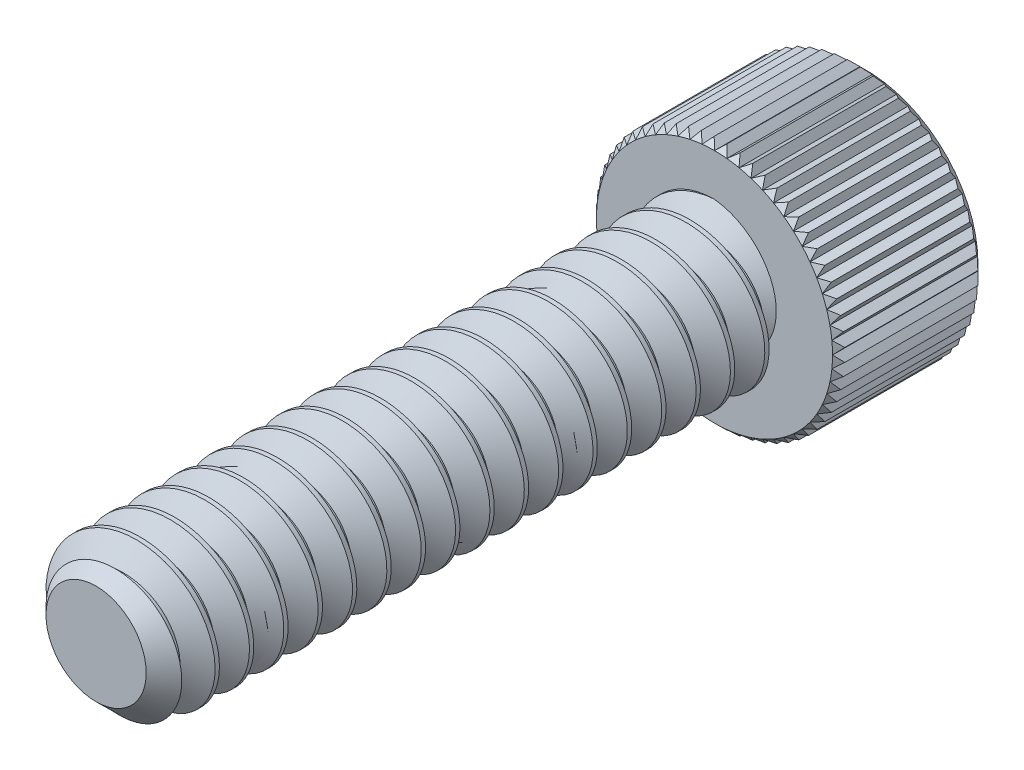
SolidWorks part; units mm, degrees
note: '?' marks a value the reader was unsure of.
ref_plane "Front Plane" through (0, 0, 0) normal (0, 0, 1) x (1, 0, 0)
ref_plane "Top Plane" through (0, 0, 0) normal (0, 1, 0) x (1, 0, 0)
ref_plane "Right Plane" through (0, 0, 0) normal (1, 0, 0) x (0, 0, -1)
sketch "Sketch0" plane through (0, 0, 0) normal (1, 0, 0) x (0, 0, -1)
  line L0 (0, 0) -> (14.2875, 0) construction
  point P2 (17.7927, 0)
  point P4 (0, 0)
  dimension "D1" = 14.2875
  dimension "D2" = 3.5052
  dimension "Min Thread" = 0
sketch "Sketch1" plane through (0, 0, 0) normal (0, 0, 1) x (1, 0, 0)
  circle A0 centre (0, 0) radius 1.7526
  dimension "OD" = 3.5052
extrude "Extrude1" add sketch "Sketch1" against normal blind 14.2875
sketch "Sketch2" plane through (0, 0, 0) normal (0, 0, 1) x (1, 0, 0)
  circle A0 centre (0, 0) radius 1.7526 construction
  circle A1 centre (0, 0) radius 1.7526
curve "Helix/Spiral1" pitch 0.7937 height 15.0812 turns 19 parameters "pitch"=0.7937
chamfer "Chamfer3" distance 0.5953 angle 45 1 edges at (1.7526, 0, 0)
sketch "Sketch3" plane through (0, 0, 0) normal (1, 0, 0) x (0, 0, -1)
  line L0 (-0.6945, 1.7526) -> (-0.3969, 1.237)
  line L1 (-0.3969, 1.237) -> (-0.2977, 1.237)
  line L2 (-0.2977, 1.237) -> (0, 1.7526)
  line L3 (-0.6945, 1.7526) -> (0, 1.7526)
  line L4 (-0.3473, 1.7526) -> (-0.3473, 1.237) construction
  line L5 (-0.5457, 1.4948) -> (-0.1488, 1.4948) construction
  line L6 (0, 1.7526) -> (0, -1.7526) construction
  dimension "D1" = 0.0992
  dimension "D2" = 0.3969
  dimension "D3" = 60
sweep "Cut-Sweep1" cut profiles "Sketch3" path "Helix/Spiral1"
sketch "Sketch5" plane through (0, 0, 0) normal (1, 0, 0) x (0, 0, -1)
  line L0 (14.2875, -1.2539) -> (14.2875, 1.2505) construction
  line L1 (14.2875, 1.7526) -> (0, 1.7526)
  line L2 (14.2875, 1.7526) -> (14.2875, 0)
  line L3 (14.2875, 0) -> (-0.6379, 0)
  line L4 (0, 0) -> (14.2875, 0) construction
  line L5 (0, 1.7526) -> (-0.6379, 0)
  line L6 (0, 0) -> (16.8275, 0) construction
  dimension "D1" = 70
  dimension "D3" = 2.54
revolve "partially thread" [suppressed] add sketch "Sketch5" angle 360 about L6
sketch "Sketch6" plane through (0, 0, -14.2875) normal (0, 0, -1) x (-1, 0, 0)
  circle A0 centre (0, 0) radius 2.8702
  dimension "head dia" = 5.7404
extrude "Extrude2" add sketch "Sketch6" along normal blind 3.5052
sketch "Sketch7" plane through (0, 0, -17.7927) normal (0, 0, -1) x (-1, 0, 0)
  line L1 (0, 1.604) -> (-1.3891, 0.802)
  line L2 (-1.3891, 0.802) -> (-1.3891, -0.802)
  line L3 (-1.3891, -0.802) -> (0, -1.604)
  line L4 (0, -1.604) -> (1.3891, -0.802)
  line L5 (1.3891, -0.802) -> (1.3891, 0.802)
  line L6 (1.3891, 0.802) -> (0, 1.604)
  circle A0 centre (0, 0) radius 1.3891 construction
  dimension "hex dia" = 2.7781
extrude "Cut-Extrude1" cut sketch "Sketch7" against normal blind 2.0836
sketch "Sketch8" plane through (0, 0, -17.7927) normal (0, 0, -1) x (-1, 0, 0)
  circle A0 centre (0, 0) radius 1.604
extrude "Cut-Extrude2" cut sketch "Sketch8" against normal through all draft 45
chamfer "Chamfer1" distance 0.287 angle 45 1 edges at (-2.8702, 0, -17.7927)
chamfer "Chamfer2" distance 0.1435 angle 45 1 edges at (-2.8702, 0, -14.2875)
sketch "Sketch9" plane through (0, 0, 0) normal (1, 0, 0) x (0, 0, -1)
  line L0 (0, 1.7526) -> (0, -1.7526) construction
  line L1 (1.9844, 1.7526) -> (1.9844, -1.7526) construction
  line L2 (17.7927, 2.8702) -> (17.7927, -2.8702) construction
  line L3 (14.2875, 2.8702) -> (14.2875, -2.8702) construction
  line L4 (14.2875, 2.7267) -> (14.2875, -2.7267) construction
  line L5 (17.7927, -2.5832) -> (17.7927, 2.5832) construction
  line L6 (14.2875, -2.8702) -> (14.2875, 2.8702) construction
  line L7 (0, 1.1573) -> (0, -1.1573) construction
  line L8 (-0.6945, 1.7526) -> (0, 1.7526) construction
  line L9 (1.9844, 0) -> (0, 0) construction
  dimension "D1" = 1.9844
sketch "Sketch10" plane through (0, 0, -14.2875) normal (0, 0, 1) x (1, 0, 0)
  line L0 (-0.3089, 3.0137) -> (0, 2.7267)
  line L1 (0, 2.7267) -> (0.3089, 3.0137)
  line L2 (0, 2.7267) -> (0, 3.0137) construction
  line L3 (-0.3089, 3.0137) -> (0.3089, 3.0137)
  line L4 (0, -2.8599) -> (0, 2.8599) construction
  line L5 (0, 0) -> (0.1502, 2.8663) construction
  line L6 (-0.1502, 2.8663) -> (0, 0) construction
  circle A2 centre (0, 0) radius 2.8702 construction
  circle A5 centre (0, 0) radius 2.7267 construction
  dimension "D1" = 6
  dimension "D2" = 0.287
extrude "Cut-Extrude3" cut sketch "Sketch10" against normal through all
pattern_circular "CirPattern1" count 60 over 360 about axis through (0, 0, 0) along (0, 0, 1) of "Cut-Extrude3"
ref_plane "Contact Plane 1" through (0, 0, -14.2875) normal (0, 0, 1) x (1, 0, 0)
ref_axis "Center Axis 1" through (0, 0, 0.8878) along (0, 0, -1)?
equation "\"D3@Helix/Spiral1\" = \"screw length@Extrude1\"+\"pitch@Helix/Spiral1\""
equation "\"D1@Sketch3\" = \"pitch@Helix/Spiral1\"*.125"
equation "\"D2@Sketch3\" = \"pitch@Helix/Spiral1\"*.5"
equation "\"D1@Cut-Extrude1\" = \"hex dia@Sketch7\"*.75"
equation "\"D1@Chamfer1\" = \"head dia@Sketch6\"*.05"
equation "\"D1@Sketch9\" = \"pitch@Helix/Spiral1\"*2.50"
equation "\"D1@Chamfer2\" = \"D1@Chamfer1\"/2"
equation "\"D1@Chamfer3\" = \"pitch@Helix/Spiral1\"*.750"
equation "\"D1@Sketch0\" = \"screw length@Extrude1\""
equation "\"D2@Sketch0\" = \"head depth@Extrude2\""
equation "\"D2@Sketch10\"=\"D1@Chamfer1\""
equation "\"D1@CirPattern1\"=\"D3@CirPattern1\"/\"D1@Sketch10\""
